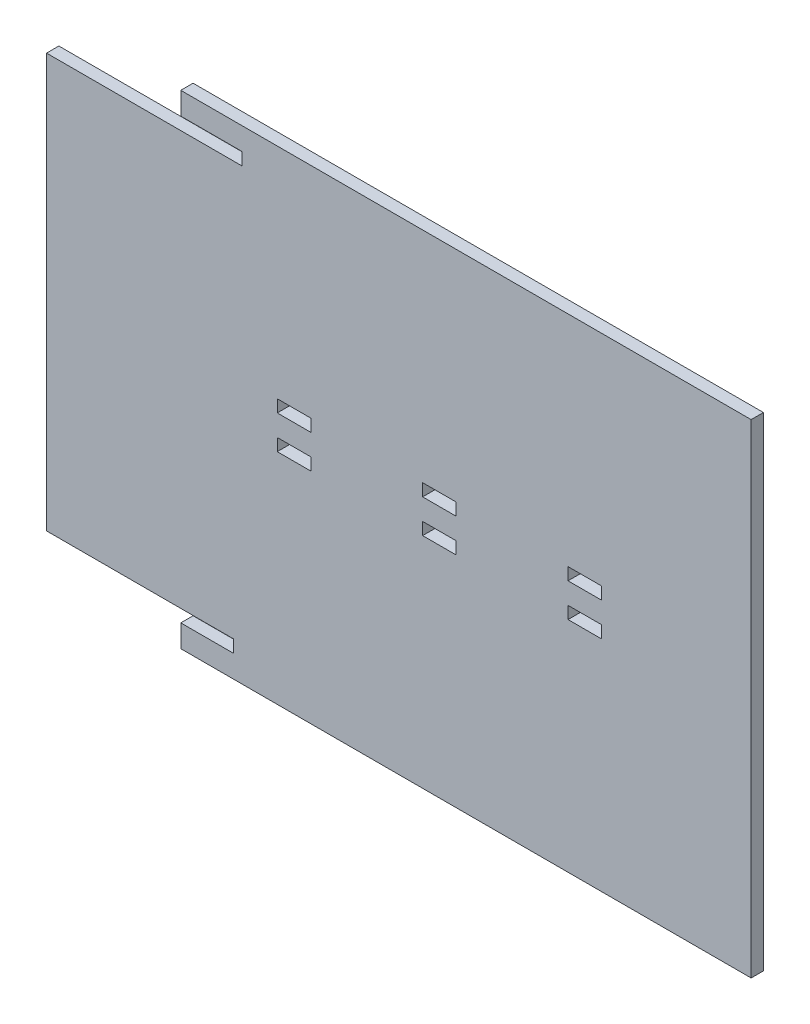
SolidWorks part; units mm, degrees
ref_plane "Alzado" through (0, 0, 0) normal (0, 0, 1) x (1, 0, 0)
ref_plane "Planta" through (0, 0, 0) normal (0, 1, 0) x (1, 0, 0)
ref_plane "Vista lateral" through (0, 0, 0) normal (1, 0, 0) x (0, 0, -1)
sketch "Croquis1" plane through (0, 0, 0) normal (0, 0, 1) x (1, 0, 0)
  line L0 (27.5261, 0.1) -> (27.5261, -216.1)
  line L1 (27.5261, -216.1) -> (-227.4739, -216.1)
  line L2 (-227.4739, -216.1) -> (-227.4739, -206.1)
  line L3 (-227.4739, -206.1) -> (-203.8311, -206.1)
  line L5 (-203.8311, -200.5) -> (-287.4739, -200.5)
  line L6 (-287.4739, -200.5) -> (-287.4739, -15.5)
  line L7 (-287.4739, -15.5) -> (-200, -15.5)
  line L8 (-200, -15.5) -> (-200, -9.9)
  line L9 (-200, -9.9) -> (-227.4739, -9.9)
  line L10 (-227.4739, -9.9) -> (-227.4739, 0.1)
  line L11 (-227.4739, 0.1) -> (27.5261, 0.1)
  line L12 (27.5261, -200.7) -> (27.5261, -15.7) construction
  line L14 (-203.8311, -206.1) -> (-203.8311, -200.5)
  line L16 (-238.3231, -200.5) -> (-269.011, -200.5) construction
  point P14 (0, 0)
  point P19 (0, 0)
  dimension "D1" = 185
  dimension "D2" = 5.6
  dimension "D3" = 5.6
  dimension "D4" = 60
  dimension "D5" = 10
  dimension "D9" = 216.2
  dimension "D10" = 196.2
  dimension "D11" = 60
extrude "Saliente-Extruir1" add sketch "Croquis1" along normal blind 5.5
sketch "Croquis2" plane through (0, 0, 5.5) normal (0, 0, 1) x (1, 0, 0)
  line L0 (-287.4739, -108) -> (79.9954, -108) construction
  line L5 (-287.4739, -15.5) -> (-287.4739, -200.5) construction
  line L6 (-54.337, -112.75) -> (-39.337, -112.75)
  line L7 (-119.337, -97.75) -> (-104.337, -97.75)
  line L8 (-184.337, -97.75) -> (-169.337, -97.75)
  line L9 (-184.337, -97.75) -> (-184.337, -103.25)
  line L10 (-184.337, -103.25) -> (-169.337, -103.25)
  line L11 (-169.337, -97.75) -> (-169.337, -103.25)
  line L28 (-119.337, -97.75) -> (-119.337, -103.25)
  line L29 (-119.337, -103.25) -> (-104.337, -103.25)
  line L30 (-104.337, -97.75) -> (-104.337, -103.25)
  line L31 (-54.337, -97.75) -> (-39.337, -97.75)
  line L32 (-54.337, -97.75) -> (-54.337, -103.25)
  line L33 (-54.337, -103.25) -> (-39.337, -103.25)
  line L34 (-39.337, -97.75) -> (-39.337, -103.25)
  line L35 (-39.337, -118.25) -> (-39.337, -112.75)
  line L36 (-54.337, -118.25) -> (-39.337, -118.25)
  line L37 (-54.337, -118.25) -> (-54.337, -112.75)
  line L38 (-104.337, -118.25) -> (-104.337, -112.75)
  line L39 (-119.337, -118.25) -> (-104.337, -118.25)
  line L40 (-119.337, -118.25) -> (-119.337, -112.75)
  line L41 (-119.337, -112.75) -> (-104.337, -112.75)
  line L42 (-184.337, -118.25) -> (-184.337, -112.75)
  line L43 (-184.337, -118.25) -> (-169.337, -118.25)
  line L44 (-169.337, -118.25) -> (-169.337, -112.75)
  line L45 (-184.337, -112.75) -> (-169.337, -112.75)
  point P12 (0, 0)
  point P13 (0, 0)
  point P18 (0, 0)
  dimension "D1" = 4.75
  dimension "D2" = 5.5
  dimension "D3" = 15
  dimension "D4" = 50
  dimension "D5" = 50
  dimension "D6" = 15
  dimension "D7" = 15
extrude "Cortar-Extruir2" cut sketch "Croquis2" against normal blind 5.5 contours L34 L31 L32 L33 | L37 L36 L35 L6 | L30 L7 L28 L29 | L41 L40 L39 L38 | L45 L42 L43 L44 | L11 L8 L9 L10 region at (-46.837, -115.5, 5.5) region at (-111.837, -100.5, 5.5) region at (-176.837, -100.5, 5.5) region at (-46.837, -100.5, 5.5) region at (-111.837, -115.5, 5.5) region at (-176.837, -115.5, 5.5)
